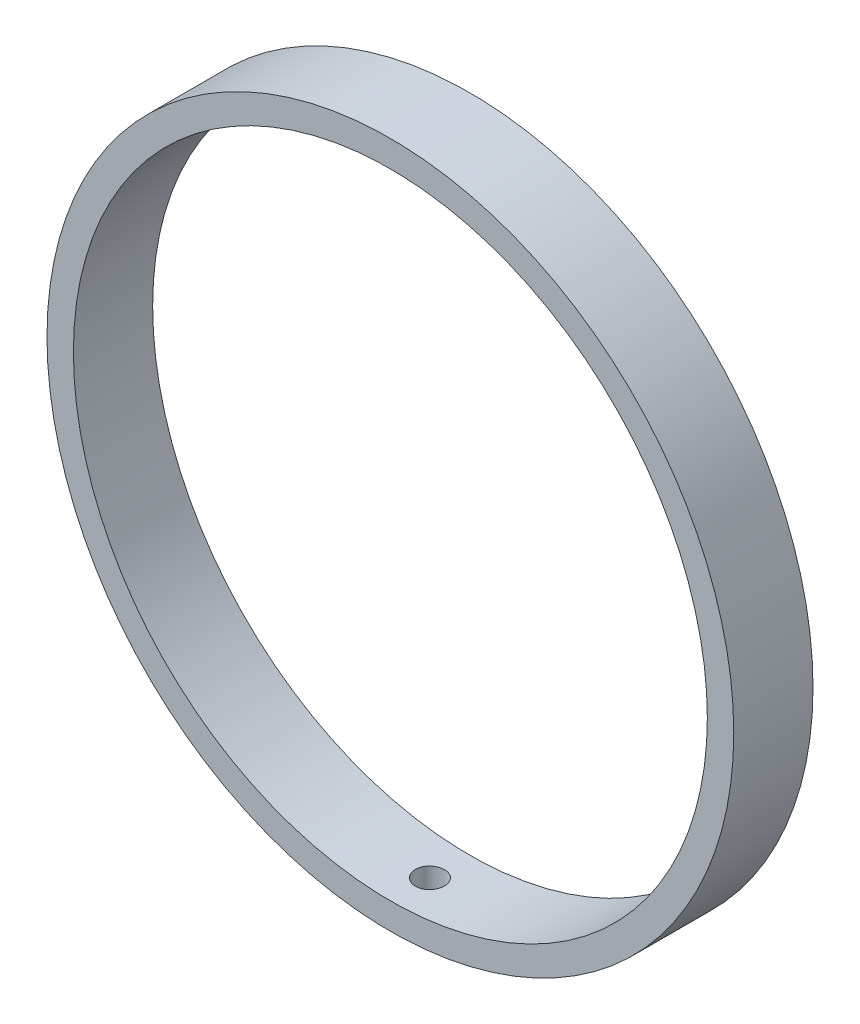
SolidWorks part; units mm, degrees
ref_plane "Front Plane" through (0, 0, 0) normal (0, 0, 1) x (1, 0, 0)
ref_plane "Top Plane" through (0, 0, 0) normal (0, 1, 0) x (1, 0, 0)
ref_plane "Right Plane" through (0, 0, 0) normal (1, 0, 0) x (0, 0, -1)
sketch "Sketch1" plane through (0, 0, 0) normal (0, 0, 1) x (1, 0, 0)
  circle A0 centre (0, 0) radius 76.2
  circle A1 centre (0, 0) radius 82.55
extrude "Boss-Extrude1" add sketch "Sketch1" along normal blind 19.05
sketch "Sketch2" plane through (0, 0, 0) normal (0, 1, 0) x (1, 0, 0)
  line L0 (76.2, 0) -> (-76.2, 0) construction
  line L1 (0, -2.0807) -> (0, -15.8358) construction
  circle A0 centre (0, -9.525) radius 3.4782
  dimension "D1" = 9.525
extrude "Cut-Extrude1" cut sketch "Sketch2" against normal through all
ref_axis "Axis1" through (0, 0, 2.0807) along (0, 0, 1)
